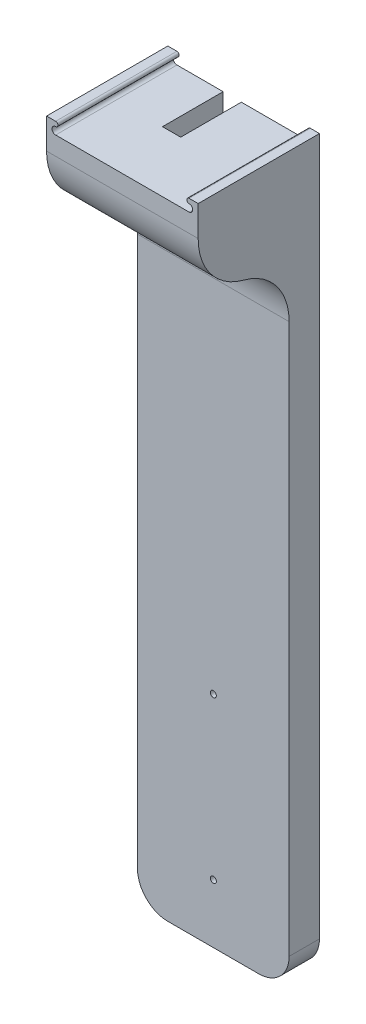
SolidWorks part; units mm, degrees
ref_plane "Přední rovina" through (0, 0, 0) normal (0, 0, 1) x (1, 0, 0)
ref_plane "Horní rovina" through (0, 0, 0) normal (0, 1, 0) x (1, 0, 0)
ref_plane "Pravá rovina" through (0, 0, 0) normal (1, 0, 0) x (0, 0, -1)
sketch "Skica1" plane through (0, 0, 0) normal (0, 0, 1) x (1, 0, 0)
  line L1 (0, 0) -> (25, 0)
  line L2 (0, 0) -> (0, 120)
  line L3 (0, 120) -> (25, 120)
  line L4 (25, 0) -> (25, 120)
  dimension "D1" = 120
  dimension "D2" = 25
extrude "Přidat vysunutím1" add sketch "Skica1" along normal blind 5
sketch "Skica2" plane through (0, 0, 0) normal (0, 0, -1) x (-1, 0, 0)
  line L0 (0, 120) -> (0, 0) construction
  line L1 (-25, 120) -> (0, 120)
  line L2 (-25, 120) -> (-25, 105)
  line L3 (-25, 105) -> (0, 105)
  line L4 (0, 120) -> (0, 105)
  dimension "D1" = 15
extrude "Přidat vysunutím2" add sketch "Skica2" against normal blind 20
fillet "Zaoblit5" radius 5 1 edges at (25, 0, 2.5)
fillet "Zaoblit6" radius 5 1 edges at (0, 0, 2.5)
sketch "Skica3" plane through (0, 0, 20) normal (0, 0, 1) x (1, 0, 0)
  line L0 (1.5, 118.04) -> (23.5, 118.04)
  line L1 (0, 120) -> (25, 120) construction
  line L4 (1.5, 120) -> (23.5, 120)
  line L5 (0, 105) -> (0, 120) construction
  line L6 (25, 120) -> (25, 105) construction
  arc A0 (23.5, 118.04) -> (23.5, 119.24) centre (23.5, 118.64) ccw
  arc A1 (23.5, 119.24) -> (23.5, 120) centre (23.5, 119.62) cw
  arc A2 (1.5, 118.04) -> (1.5, 119.24) centre (1.5, 118.64) cw
  arc A3 (1.5, 119.24) -> (1.5, 120) centre (1.5, 119.62) ccw
  dimension "D1" = 0.6
  dimension "D2" = 0.6
  dimension "D3" = 0.38
  dimension "D4" = 0.38
  dimension "D5" = 1.5
  dimension "D6" = 1.5
  dimension "D7" = 1.96
extrude "Odebrat vysunutím2" cut sketch "Skica3" against normal blind 20
fillet "Zaoblit7" radius 10 1 edges at (12.5, 105, 20)
fillet "Zaoblit8" radius 10 1 edges at (12.5, 105, 5)
sketch "Skica4" plane through (0, 118.04, 0) normal (0, 1, 0) x (1, 0, 0)
  line L0 (1.5, 0) -> (23.5, 0) construction
  line L1 (9.12, 0) -> (12.12, 0)
  line L2 (9.12, 0) -> (9.12, -10)
  line L3 (9.12, -10) -> (12.12, -10)
  line L4 (12.12, 0) -> (12.12, -10)
  line L5 (23.12, 0) -> (23.12, -20) construction
  dimension "D1" = 0
  dimension "D2" = 10
  dimension "D3" = 3
  dimension "D4" = 11
extrude "Odebrat vysunutím3" cut sketch "Skica4" against normal blind 3
sketch "Skica5" plane through (0, 0, 0) normal (0, 0, 1) x (1, 0, 0)
  line L0 (9, 21) -> (16, 21)
  line L1 (16, 21) -> (14, 43)
  line L3 (11, 43) -> (9, 21)
  line L4 (11, 43) -> (14, 43)
  line L5 (9, 21) -> (10.5, 5)
  line L6 (10.5, 5) -> (14.5, 5)
  line L7 (14.5, 5) -> (16, 21)
  line L9 (5, 0) -> (20, 0) construction
  line L10 (5.5, 24) -> (19.5, 24)
  line L11 (5.5, 24) -> (5.5, 20)
  line L12 (5.5, 20) -> (19.5, 20)
  line L13 (19.5, 24) -> (19.5, 20)
  arc A0 (5.5, 24) -> (5.5, 20) centre (5.5, 22) ccw
  arc A1 (19.5, 24) -> (19.5, 20) centre (19.5, 22) cw
  point P2 (12.5, 43)
  point P5 (12.5, 21)
  point P6 (12.5, 5)
  point P11 (12.5, 0)
  point P16 (12.5, 24)
  dimension "D1" = 7
  dimension "D2" = 3
  dimension "D3" = 22
  dimension "D4" = 16
  dimension "D5" = 5
  dimension "D6" = 4
  dimension "D7" = 19
  dimension "D8" = 14
  dimension "D9" = 4
extrude "Odebrat vysunutím4" cut sketch "Skica5" along normal blind 2 contours L3 L10 L1 L4 | L11 A0 | L11 L12 L5 L3 L10 | L10 L3 L0 L1 | L5 L12 L7 L0 | L13 L10 L1 L7 L12 | A1 L13 | L12 L5 L6 L7 region at (12.5, 22.4797, 0) region at (7.3079, 22.0229, 0) region at (12.5, 20.5023, 0) region at (17.6921, 22.0229, 0) region at (12.5, 32.3429, 0) region at (12.5, 13.1503, 0) region at (4.6512, 22, 0) region at (20.3488, 22, 0)
sketch "Skica7" plane through (0, 0, 2) normal (0, 0, -1) x (-1, 0, 0)
  line L0 (-11, 43) -> (-14, 43) construction
  line L1 (-21.5, 22) -> (-3.5, 22) construction
  circle A0 centre (-12.5, 36.2) radius 0.5
  circle A1 centre (-12.5, 9.7) radius 0.5
  arc A2 (-19.5, 24) -> (-19.5, 20) centre (-19.5, 22) ccw construction
  arc A3 (-5.5, 20) -> (-5.5, 24) centre (-5.5, 22) ccw construction
  point P9 (-12.5, 43)
  dimension "D1" = 1
  dimension "D2" = 1
  dimension "D4" = 12.3
  dimension "D3" = 14.2
extrude "Odebrat vysunutím5" cut sketch "Skica7" along normal offset from surface (2.8 mm away) 0.2 from surface up to face at (12.5, 22.6667, 2) starting at face at (12.5, 33.1998, 5)
sketch "Skica8" plane through (0, 0, 2) normal (0, 0, -1) x (-1, 0, 0)
  line L0 (-12.5, 43) -> (-12.5, 5) construction
  line L1 (-11, 43) -> (-14, 43) construction
  line L2 (-10.5, 5) -> (-14.5, 5) construction
  line L3 (-21.5, 22) -> (-3.5, 22) construction
  circle A0 centre (-12.5, 22) radius 3.75
  arc A1 (-19.5, 24) -> (-19.5, 20) centre (-19.5, 22) ccw construction
  arc A2 (-5.5, 20) -> (-5.5, 24) centre (-5.5, 22) ccw construction
  dimension "D3" = 7.5
  dimension "D1" = 0
  dimension "D2" = 0
extrude "Odebrat vysunutím6" cut sketch "Skica8" against normal blind 2
